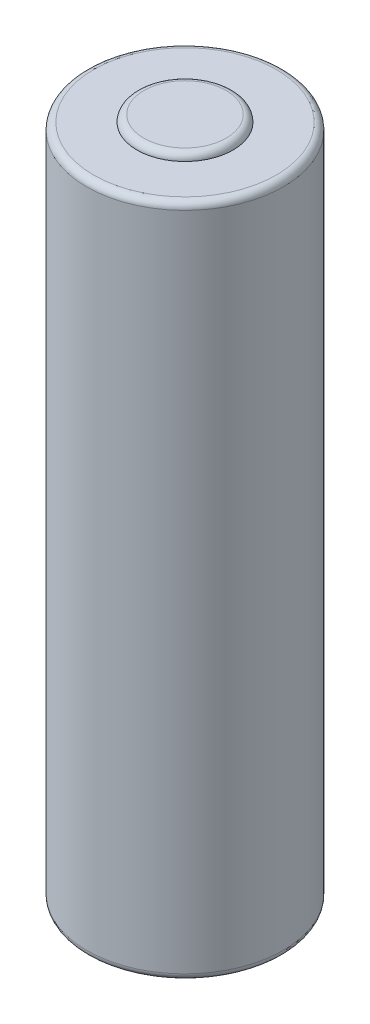
SolidWorks part; units mm, degrees
material "Custom Plastic"
ref_plane "Front Plane" through (0, 0, 0) normal (0, 0, 1) x (1, 0, 0)
ref_plane "Top Plane" through (0, 0, 0) normal (0, 1, 0) x (1, 0, 0)
ref_plane "Right Plane" through (0, 0, 0) normal (1, 0, 0) x (0, 0, -1)
sketch "Sketch1" plane through (0, 0, 0) normal (0, 1, 0) x (1, 0, 0)
  circle A0 centre (0, 0) radius 7.15
  dimension "D1" = 14.3
extrude "Boss-Extrude1" add sketch "Sketch1" along normal mid plane 49.127
sketch "Sketch2" plane through (0, 24.5635, 0) normal (0, 1, 0) x (1, 0, 0)
  circle A0 centre (0, 0) radius 3.5
  dimension "D1" = 7
extrude "Boss-Extrude2" add sketch "Sketch2" along normal blind 0.5
fillet "Fillet1" radius 0.5 3 edges at (0, 25.0635, 3.5) (0, -24.5635, 7.15) (0, 24.5635, 7.15)
